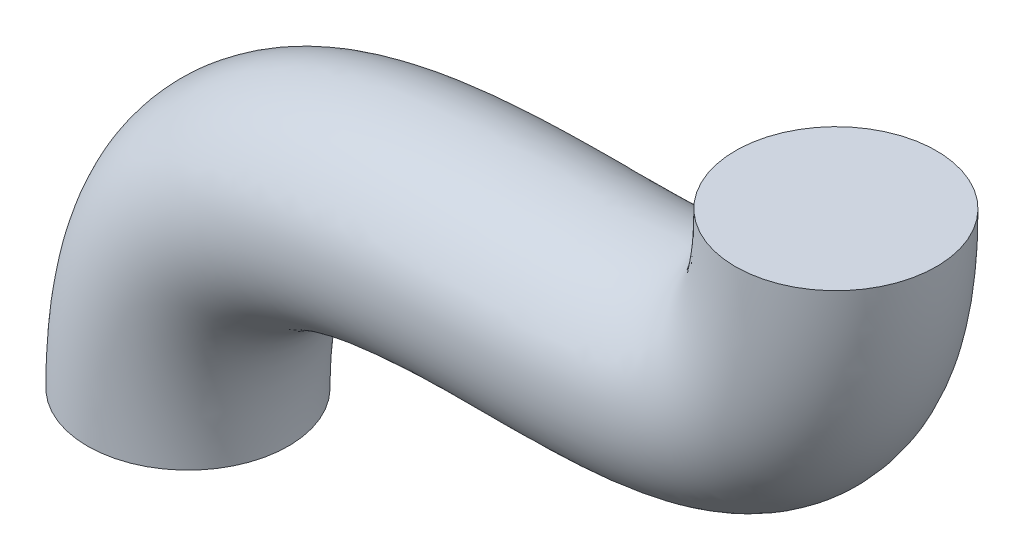
SolidWorks part; units mm, degrees
ref_plane "Front Plane" through (0, 0, 0) normal (0, 0, 1) x (1, 0, 0)
ref_plane "Top Plane" through (0, 0, 0) normal (0, 1, 0) x (1, 0, 0)
ref_plane "Right Plane" through (0, 0, 0) normal (1, 0, 0) x (0, 0, -1)
sketch "Sketch1" plane through (0, 0, 0) normal (0, 0, 1) x (1, 0, 0)
  spline S0 degree 3 poles (-28.9914, -63.3302) (-28.9914, -52.376) (-15.0991, -50.4655) (0, -51.9065) (0, -41.8802) knots 0 0 0 0 0.542373 1 1 1 1
  point P2 (-13.5668, -51.2895)
  dimension "D1" = 21.45
  dimension "D4" = 12.0407
  dimension "D5" = 15.4247
ref_plane "Plane1" through (0, -63.3302, 0) normal (0, 1, 0) x (1, 0, 0)
sketch "Sketch2" plane through (0, -63.3302, 0) normal (0, 1, 0) x (1, 0, 0)
  circle A0 centre (-28.9914, 0) radius 4.4958
  dimension "D1" = 8.9916
sweep "Sweep1" add profiles "Sketch2" path "Sketch1"
